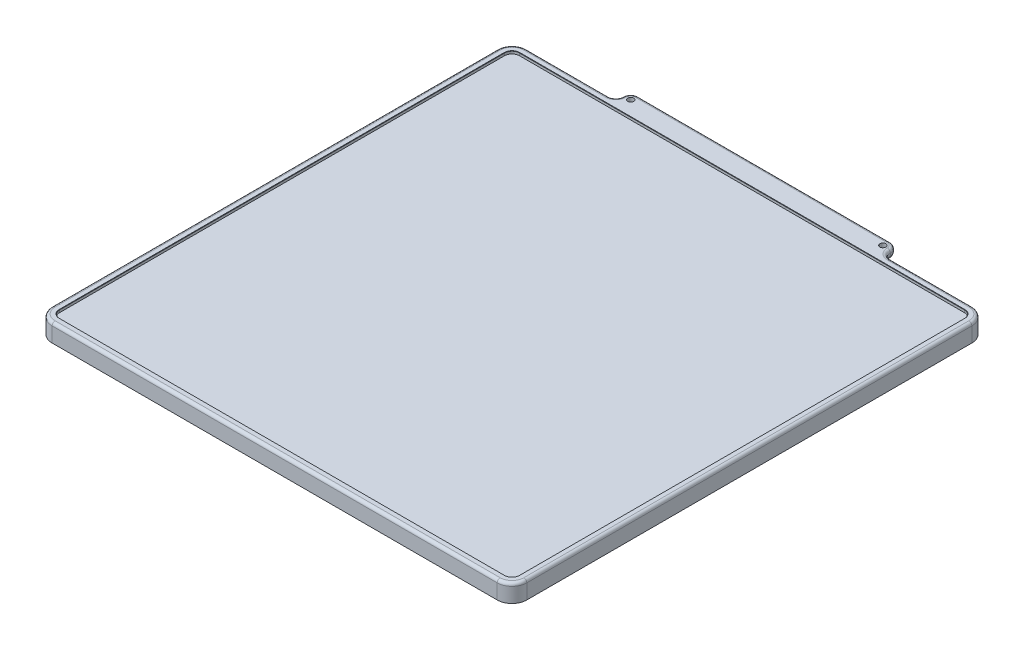
SolidWorks part; units mm, degrees
material "3.3547 (EN-AW 5083)"
ref_plane "Ebene vorne" through (0, 0, 0) normal (0, 0, 1) x (1, 0, 0)
ref_plane "Ebene oben" through (0, 0, 0) normal (0, 1, 0) x (1, 0, 0)
ref_plane "Ebene rechts" through (0, 0, 0) normal (1, 0, 0) x (0, 0, -1)
sketch "Skizze1" plane through (0, 0, 0) normal (0, 1, 0) x (1, 0, 0)
  line L0 (-45, 80) -> (-45, 85)
  line L1 (75, -80) -> (-75, -80)
  line L2 (80, -75) -> (80, 75)
  line L3 (75, 80) -> (-75, 80)
  line L4 (-80, -75) -> (-80, 75)
  line L5 (80, -80) -> (-80, 80) construction
  line L6 (80, 80) -> (-80, -80) construction
  line L7 (-45, 85) -> (45, 85)
  line L8 (45, 85) -> (45, 80)
  line L9 (0, 85) -> (0, 80) construction
  arc A0 (-75, -80) -> (-80, -75) centre (-75, -75) cw
  arc A1 (75, -80) -> (80, -75) centre (75, -75) ccw
  arc A2 (80, 75) -> (75, 80) centre (75, 75) ccw
  arc A3 (-75, 80) -> (-80, 75) centre (-75, 75) ccw
  point P0 (0, 0)
  dimension "D3" = 5
  dimension "D1" = 160
  dimension "D2" = 160
  dimension "D4" = 90
  dimension "D5" = 5
extrude "Aufsatz-Linear austragen1" add sketch "Skizze1" along normal blind 6 contours L8 L7 L0 L3 | L3 A3 L4 A0 L1 A1 L2 A2 region at (0, 0, -82.5) region at (0, 0, 0)
fillet "Verrundung3" radius 2.5 4 edges at (45, 3, -80) (45, 3, -85) (-45, 3, -85) (-45, 3, -80)
fillet "Verrundung1" radius 1 14 edges at (-78.5355, 6, 78.5355) (0, 6, 80) (78.5355, 6, 78.5355) (80, 6, 0) (78.5355, 6, -78.5355) (61.25, 6, -80) (45.7322, 6, -80.7322) (44.2678, 6, -84.2678) (0, 6, -85) (-44.2678, 6, -84.2678) (-45.7322, 6, -80.7322) (-61.25, 6, -80) (-78.5355, 6, -78.5355) (-80, 6, 0)
sketch "Skizze3" plane through (0, 6, 0) normal (0, 1, 0) x (1, 0, 0)
  line L0 (-80, -75) -> (-80, 75) construction
  line L1 (75, -77.5) -> (-75, -77.5)
  line L2 (77.5, -75) -> (77.5, 75)
  line L3 (75, 77.5) -> (-75, 77.5)
  line L4 (-77.5, -75) -> (-77.5, 75)
  line L5 (77.5, -77.5) -> (-77.5, 77.5) construction
  line L6 (77.5, 77.5) -> (-77.5, -77.5) construction
  arc A0 (-75, -77.5) -> (-77.5, -75) centre (-75, -75) cw
  arc A1 (75, -77.5) -> (77.5, -75) centre (75, -75) ccw
  arc A2 (77.5, 75) -> (75, 77.5) centre (75, 75) ccw
  arc A3 (-75, 77.5) -> (-77.5, 75) centre (-75, 75) ccw
  point P0 (0, 0)
  dimension "D2" = 2.5
  dimension "D1" = 2.5
extrude "Schnitt-Linear austragen2" cut sketch "Skizze3" against normal blind 0.9
chamfer "Fase1" distance 0.1 angle 45 8 edges at (76.7678, 6, 76.7678) (77.5, 6, 0) (0, 6, 77.5) (76.7678, 6, -76.7678) (-76.7678, 6, 76.7678) (0, 6, -77.5) (-77.5, 6, 0) (-76.7678, 6, -76.7678)
sketch "Skizze4" plane through (0, 0, -85) normal (0, 0, -1) x (-1, 0, 0)
  line L0 (47.5, 5) -> (47.5, 0) construction
  line L1 (-47.5, 0) -> (47.5, 0)
  line L2 (-47.5, 0) -> (-47.5, 3)
  line L3 (-47.5, 3) -> (47.5, 3)
  line L4 (47.5, 0) -> (47.5, 3)
  line L5 (-47.5, 0) -> (-47.5, 5) construction
  line L6 (42.5, 0) -> (-42.5, 0) construction
  dimension "D1" = 3
extrude "Schnitt-Linear austragen3" cut sketch "Skizze4" against normal up to surface (5 mm away) up to face at (61.25, 2.5, -80)
fillet "Verrundung4" radius 1.25 6 edges at (-45.7322, 3, -80.7322) (-44.2678, 3, -84.2678) (0, 3, -85) (44.2678, 3, -84.2678) (45.7322, 3, -80.7322) (0, 3, -80)
sketch "Skizze5" plane through (0, 6, 0) normal (0, 1, 0) x (1, 0, 0)
  circle A0 centre (-42.5, 82.5) radius 1
  circle A1 centre (42.5, 82.5) radius 1
  dimension "D1" = 2
extrude "Schnitt-Linear austragen4" cut sketch "Skizze5" against normal up to next
